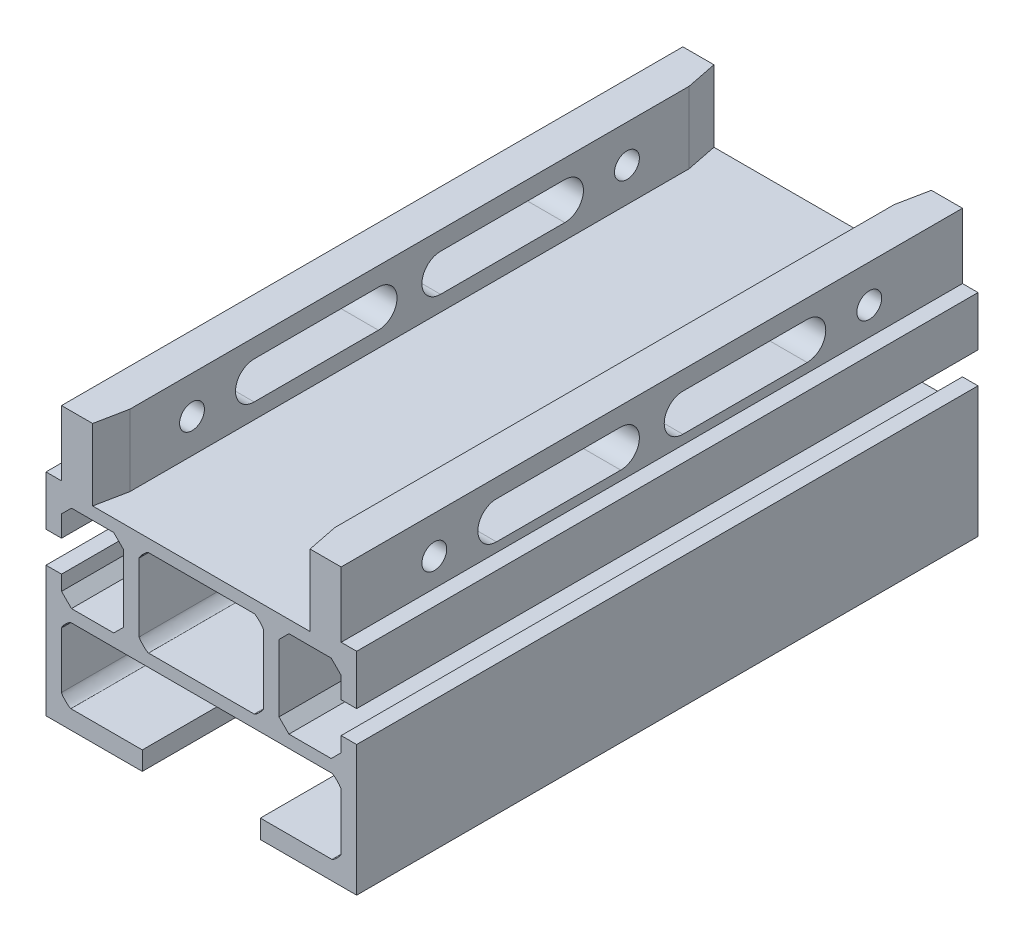
SolidWorks part; units mm, degrees
material "ABS generico"
ref_plane "Piano frontale" through (0, 0, 0) normal (0, 0, 1) x (1, 0, 0)
ref_plane "Piano superiore" through (0, 0, 0) normal (0, 1, 0) x (1, 0, 0)
ref_plane "Piano destro" through (0, 0, 0) normal (1, 0, 0) x (0, 0, -1)
sketch "Schizzo1" plane through (0, 0, 0) normal (0, 0, 1) x (1, 0, 0)
  line L0 (-22.5, -9) -> (22.5, -9)
  line L2 (16.5, 9) -> (-16.5, 9)
  line L4 (-40.4032, 0) -> (40.4032, 0) construction
  line L5 (-25, 10) -> (-25, 2)
  line L6 (-25, -24) -> (-9.5, -24)
  line L7 (-9.5, -24) -> (-9.5, -21)
  line L8 (-9.5, -21) -> (-22.5, -21)
  line L9 (-22.5, -21) -> (-22.5, -9)
  line L14 (9.5, -21) -> (9.5, -24)
  line L15 (9.5, -24) -> (25, -24)
  line L16 (25, -24) -> (25, -3)
  line L21 (22.5, -21) -> (9.5, -21)
  line L22 (-9.5, -24) -> (9.5, -24) construction
  line L23 (0, -24) -> (0, 0) construction
  line L25 (22.5, -9) -> (22.5, -21)
  line L26 (-25, 10) -> (-22.5, 10)
  line L27 (-22.5, 10) -> (-22.5, 20.5)
  line L28 (-22.5, 20.5) -> (-16.5, 20.5)
  line L29 (-16.5, 20.5) -> (-16.5, 9)
  line L30 (16.5, 9) -> (16.5, 20.5)
  line L31 (16.5, 20.5) -> (22.5, 20.5)
  line L32 (22.5, 20.5) -> (22.5, 10)
  line L33 (22.5, 10) -> (25, 10)
  line L34 (-25, -7) -> (25, -7) construction
  line L35 (-22.5, 7) -> (-12.5, 7)
  line L36 (-22.5, 7) -> (-22.5, 2)
  line L37 (-22.5, -7) -> (-12.5, -7)
  line L38 (-12.5, 7) -> (-12.5, -7)
  line L39 (12.5, 7) -> (22.5, 7)
  line L40 (12.5, 7) -> (12.5, -7)
  line L41 (12.5, -7) -> (22.5, -7)
  line L42 (22.5, 7) -> (22.5, 2)
  line L43 (-25, 2) -> (-22.5, 2)
  line L44 (-25, -3) -> (-22.5, -3)
  line L45 (25, -3) -> (22.5, -3)
  line L46 (22.5, 2) -> (25, 2)
  line L47 (-25, -3) -> (-25, -24)
  line L48 (25, 2) -> (25, 10)
  line L49 (-25, 2) -> (-25, -3) construction
  line L50 (25, 2) -> (25, -3) construction
  line L51 (-22.5, -3) -> (-22.5, -7)
  line L52 (22.5, -3) -> (22.5, -7)
  line L54 (-10, 7) -> (10, 7)
  line L55 (-10, 7) -> (-10, -7)
  line L56 (-10, -7) -> (10, -7)
  line L57 (10, 7) -> (10, -7)
  point P6 (0, 0)
  point P46 (-12.5, 0)
  point P51 (0, -7)
  point P52 (-23.75, 2)
  dimension "D1" = 18
  dimension "D2" = 9
  dimension "D3" = 15
  dimension "D4" = 50
  dimension "D5" = 3
  dimension "D6" = 2.5
  dimension "D7" = 1
  dimension "D8" = 2.5
  dimension "D9" = 6
  dimension "D10" = 15.5
  dimension "D11" = 11.5
  dimension "D12" = 14
  dimension "D13" = 10
  dimension "D14" = 20
  dimension "D15" = 5
  dimension "D16" = 5
extrude "Estrusione-Estrusione1" add sketch "Schizzo1" along normal blind 100
fillet "Raccordo1" radius 1.5 8 edges at (-10, -7, 50) (-10, 7, 50) (10, 7, 50) (10, -7, 50) (22.5, -21, 50) (22.5, -9, 50) (-22.5, -9, 50) (-22.5, -21, 50) conic rho 0.15
chamfer "Smusso1" distance 1.6 angle 45 8 edges at (22.5, -7, 50) (12.5, -7, 50) (22.5, 7, 50) (12.5, 7, 50) (-22.5, 7, 50) (-12.5, 7, 50) (-12.5, -7, 50) (-22.5, -7, 50)
sketch "Schizzo2" plane through (-22.5, 0, 0) normal (-1, 0, 0) x (0, 0, 1)
  line L0 (25, 14.5) -> (45, 14.5) construction
  line L1 (25, 17.5) -> (45, 17.5)
  line L2 (25, 11.5) -> (45, 11.5)
  line L3 (55, 14.5) -> (75, 14.5) construction
  line L4 (55, 17.5) -> (75, 17.5)
  line L5 (55, 11.5) -> (75, 11.5)
  line L6 (15, 14.5) -> (85, 14.5) construction
  line L7 (100, 20.5) -> (0, 20.5) construction
  line L8 (100, 20.5) -> (100, 10) construction
  circle A0 centre (85, 14.5) radius 2
  circle A1 centre (15, 14.5) radius 2
  arc A2 (25, 17.5) -> (25, 11.5) centre (25, 14.5) ccw
  arc A3 (45, 11.5) -> (45, 17.5) centre (45, 14.5) ccw
  arc A4 (55, 17.5) -> (55, 11.5) centre (55, 14.5) ccw
  arc A5 (75, 11.5) -> (75, 17.5) centre (75, 14.5) ccw
  point P6 (35, 14.5)
  point P11 (65, 14.5)
  dimension "D6" = 4
  dimension "D1" = 6
  dimension "D2" = 20
  dimension "D3" = 20
  dimension "D4" = 70
  dimension "D5" = 15
  dimension "D7" = 20
  dimension "D8" = 6
extrude "Taglio-Estrusione1" cut sketch "Schizzo2" against normal blind 100
chamfer "Smusso2" distance 5 angle 11.31 2 edges at (16.5, 14.75, 100) (-16.5, 14.75, 100) first distance on face at (16.5, 16.5, 85) first distance on face at (-16.5, 12.5, 85)
chamfer "Smusso3" distance 5 angle 11.31 2 edges at (-16.5, 14.75, 0) (16.5, 14.75, 0) first distance on face at (-16.5, 12.5, 85) first distance on face at (16.5, 16.5, 85)
